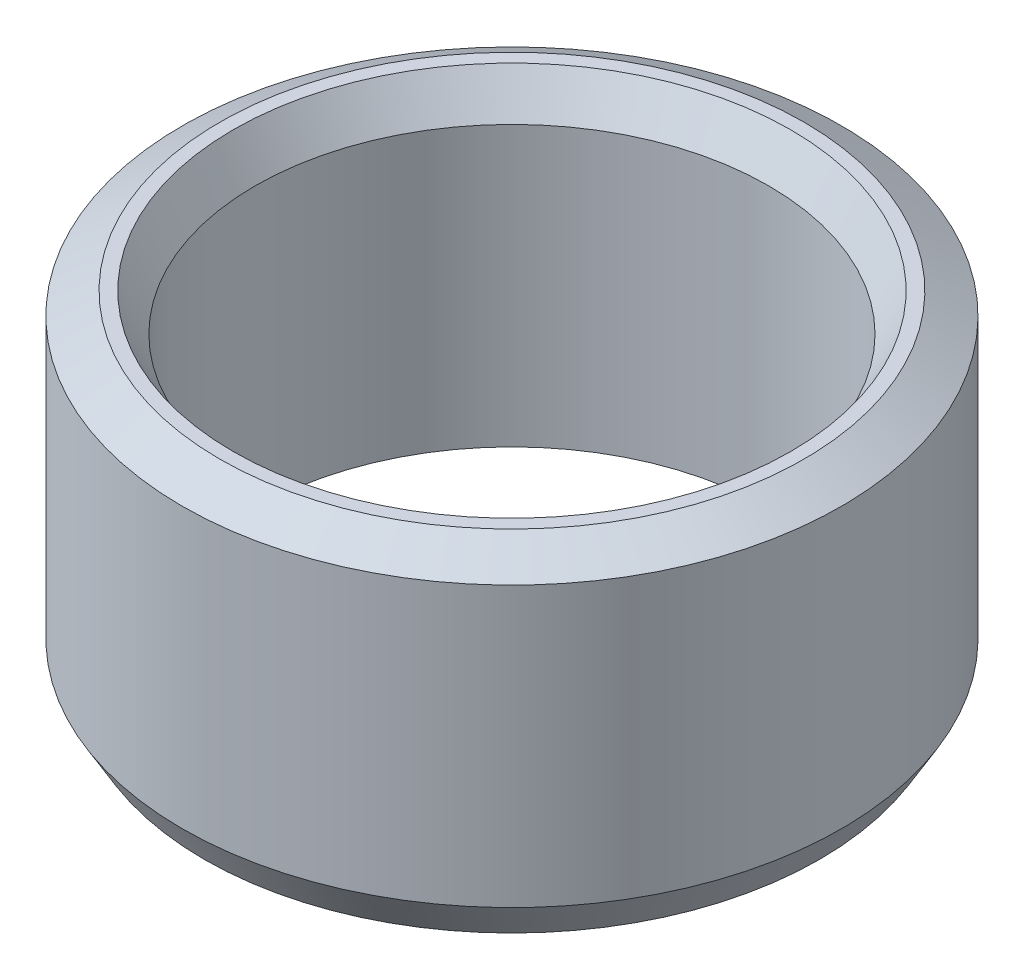
SolidWorks part; units mm, degrees
ref_plane "Front Plane" through (0, 0, 0) normal (0, 0, 1) x (1, 0, 0)
ref_plane "Top Plane" through (0, 0, 0) normal (0, 1, 0) x (1, 0, 0)
ref_plane "Right Plane" through (0, 0, 0) normal (1, 0, 0) x (0, 0, -1)
sketch "Sketch1" plane through (0, 0, 0) normal (0, 1, 0) x (1, 0, 0)
  circle A0 centre (0, 0) radius 55
  dimension "SLEEVE_OD" = 110
extrude "Boss-Extrude1" add sketch "Sketch1" along normal blind 56.5471
sketch "Sketch2" plane through (0, 0, 0) normal (0, 1, 0) x (1, 0, 0)
  circle A0 centre (0, 0) radius 42.8493
  dimension "BORE_D" = 85.6985
extrude "Cut-Extrude1" cut sketch "Sketch2" along normal through all
chamfer "Chamfer1" distance 3.6669 angle 59.682 4 edges at (0, 56.5471, 42.8493) (0, 0, 42.8493) (0, 0, 55) (0, 56.5471, 55) first distance on face at (0, 56.5471, 42.8493) first distance on face at (0, 0, 42.8493) first distance on face at (0, 56.5471, 55)
